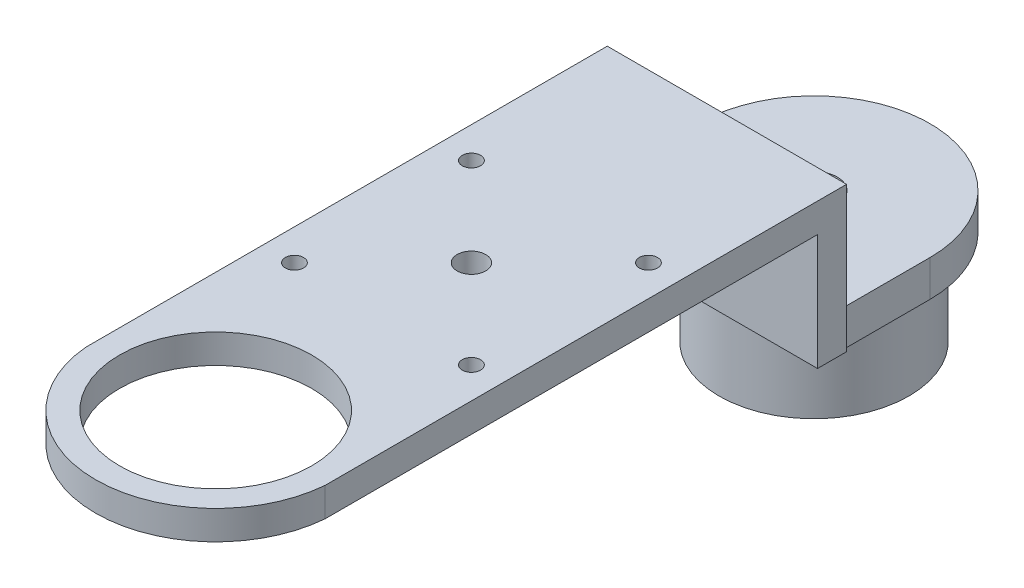
SolidWorks part; units mm, degrees
ref_plane "Front Plane" through (0, 0, 0) normal (0, 0, 1) x (1, 0, 0)
ref_plane "Top Plane" through (0, 0, 0) normal (0, 1, 0) x (1, 0, 0)
ref_plane "Right Plane" through (0, 0, 0) normal (1, 0, 0) x (0, 0, -1)
sketch "Sketch1" plane through (0, 0, 0) normal (0, 1, 0) x (1, 0, 0)
  line L0 (0, 60) -> (0, -60) construction
  line L1 (-20.955, 60) -> (20.955, 60)
  line L2 (-20.955, 60) -> (-20.955, -60)
  line L3 (-20.955, -60) -> (20.955, -60)
  line L4 (20.955, 60) -> (20.955, -60)
  line L5 (-20.955, 60) -> (20.955, -60) construction
  line L6 (-20.955, -60) -> (20.955, 60) construction
  line L7 (-15.5, 15.5) -> (15.5, 15.5) construction
  line L8 (-15.5, 15.5) -> (-15.5, -15.5) construction
  line L9 (-15.5, -15.5) -> (15.5, -15.5) construction
  line L10 (15.5, 15.5) -> (15.5, -15.5) construction
  line L11 (-15.5, 15.5) -> (15.5, -15.5) construction
  line L12 (-15.5, -15.5) -> (15.5, 15.5) construction
  line L13 (-20.955, 0) -> (20.955, 0) construction
  point P0 (0, 0)
  point P6 (0, 0)
  point P19 (0, 0)
  dimension "D1" = 120
  dimension "D2" = 41.91
  dimension "D3" = 31
extrude "Boss-Extrude1" add sketch "Sketch1" along normal blind 5.08
sketch "Sketch2" plane through (0, 0, -60) normal (0, 0, -1) x (-1, 0, 0)
  line L0 (20.955, 5.08) -> (20.955, 0) construction
  line L1 (-20.955, 5.08) -> (20.955, 5.08)
  line L2 (-20.955, 5.08) -> (-20.955, -20.32)
  line L3 (-20.955, -20.32) -> (20.955, -20.32)
  line L4 (20.955, 5.08) -> (20.955, -20.32)
  dimension "D1" = 25.4
extrude "Boss-Extrude2" add sketch "Sketch2" along normal blind 5.08
sketch "Sketch6" plane through (0, -20.32, 0) normal (0, -1, 0) x (1, 0, 0)
  line L0 (0, -60) -> (0, -100.6654) construction
  line L1 (20.955, -60) -> (-20.955, -60) construction
  line L2 (20.32, -80.3327) -> (20.32, -60.0127)
  line L3 (20.32, -60.0127) -> (-20.32, -60.0127)
  line L4 (-20.32, -60.0127) -> (-20.32, -80.3327)
  arc A0 (-20.32, -80.3327) -> (20.32, -80.3327) centre (0, -80.3327) ccw
  point P5 (0, -80.3327)
  dimension "D2" = 20.32
  dimension "D1" = 40.6654
extrude "Boss-Extrude3" add sketch "Sketch6" against normal blind 6.35
sketch "Sketch7" plane through (0, 0, 0) normal (0, -1, 0) x (1, 0, 0)
  line L0 (0, -80.3327) -> (0, -20.3327) construction
  line L1 (15.5, -20.3327) -> (-15.5, -20.3327) construction
  line L2 (15.5, -35.8327) -> (-15.5, -35.8327) construction
  line L3 (15.5, -35.8327) -> (15.5, -4.8327) construction
  line L4 (15.5, -4.8327) -> (-15.5, -4.8327) construction
  line L5 (-15.5, -35.8327) -> (-15.5, -4.8327) construction
  line L6 (15.5, -35.8327) -> (-15.5, -4.8327) construction
  line L7 (15.5, -4.8327) -> (-15.5, -35.8327) construction
  circle A0 centre (0, -20.3327) radius 2.5
  circle A1 centre (15.5, -35.8327) radius 1.6
  circle A2 centre (-15.5, -35.8327) radius 1.6
  circle A3 centre (-15.5, -4.8327) radius 1.6
  circle A4 centre (15.5, -4.8327) radius 1.6
  dimension "D2" = 5
  dimension "D5" = 3.2
  dimension "D1" = 60
  dimension "D3" = 31
  dimension "D4" = 31
extrude "Cut-Extrude1" cut sketch "Sketch7" against normal through all
sketch "Sketch8" plane through (0, -20.32, 0) normal (0, -1, 0) x (1, 0, 0)
  circle A0 centre (0, -80.3327) radius 16.637
  circle A1 centre (0, -80.3327) radius 11.43
  dimension "D1" = 33.274
  dimension "D2" = 22.86
extrude "Boss-Extrude4" add sketch "Sketch8" along normal blind 16.51
sketch "Sketch9" plane through (0, -20.32, 0) normal (0, -1, 0) x (1, 0, 0)
  circle A0 centre (0, -80.3327) radius 4.0957
  dimension "D1" = 8.1915
extrude "Cut-Extrude2" cut sketch "Sketch9" against normal through all
sketch "Sketch10" plane through (0, 5.08, 0) normal (0, 1, 0) x (-1, 0, 0)
  line L0 (0, -20.3327) -> (0, 60) construction
  line L1 (20.955, 60) -> (-20.955, 60) construction
  line L2 (-20.955, 60) -> (-20.955, -65.08) construction
  line L3 (20.955, -65.08) -> (20.955, 60) construction
  line L4 (-20.955, 26.2333) -> (-65.5469, 51.8749)
  line L5 (-65.5469, 51.8749) -> (-15.8449, 69.7979)
  line L6 (-15.8449, 69.7979) -> (48.5181, 69.7979)
  line L7 (48.5181, 69.7979) -> (38.7729, 26.2333)
  line L8 (38.7729, 26.2333) -> (20.955, 26.2333)
  arc A0 (-20.955, 26.2333) -> (20.955, 26.2333) centre (0, 24.4677) cw
  circle A1 centre (0, 24.4677) radius 16.8275
  circle A2 centre (0, -80.3327) radius 4.0957 construction
  circle A3 centre (0, -80.3327) radius 4.0957 construction
  dimension "D1" = 33.655
  dimension "D2" = 104.8004
extrude "Cut-Extrude3" cut sketch "Sketch10" against normal through all
